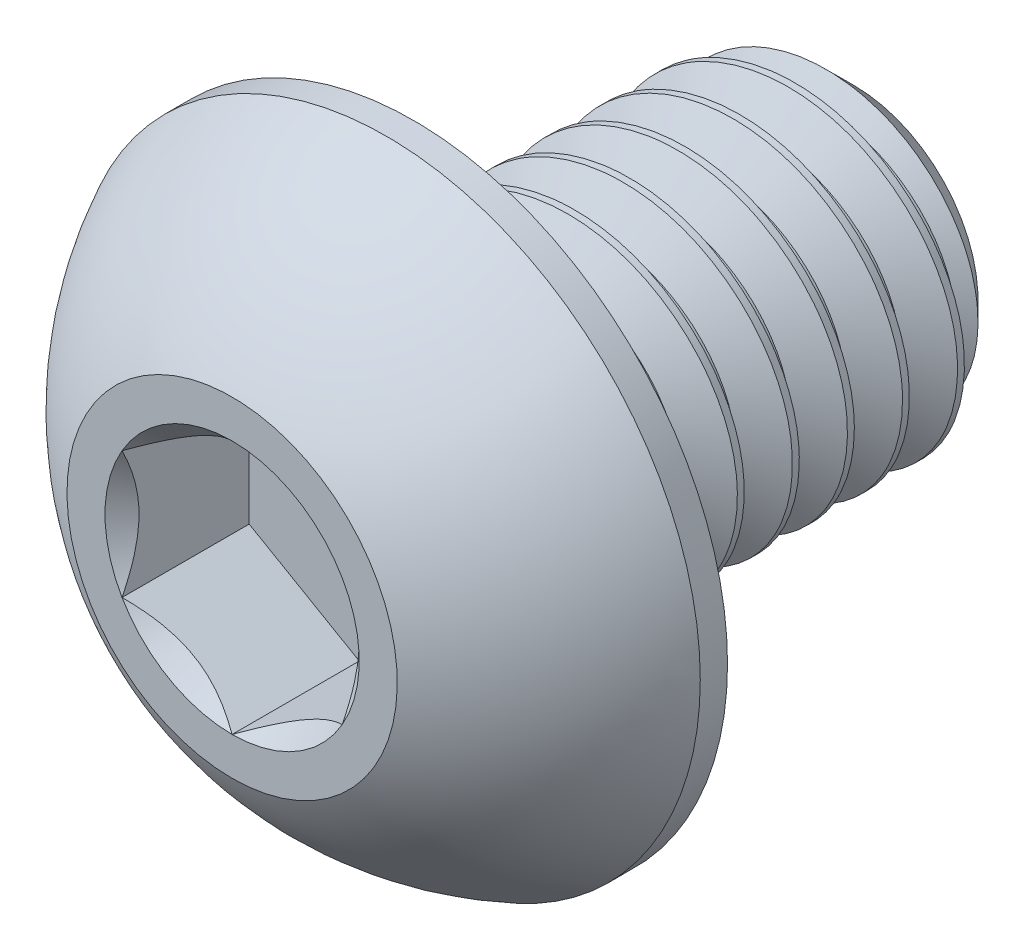
SolidWorks part; units mm, degrees
ref_plane "Front" through (0, 0, 0) normal (0, 0, 1) x (1, 0, 0)
ref_plane "Top" through (0, 0, 0) normal (0, 1, 0) x (1, 0, 0)
ref_plane "Right" through (0, 0, 0) normal (1, 0, 0) x (0, 0, -1)
sketch "Sketch1" plane through (0, 0, 0) normal (1, 0, 0) x (0, 0, -1)
  line L2 (1.65, 1.5) -> (5.65, 1.5)
  line L3 (5.65, 1.5) -> (5.65, 0)
  line L4 (5.65, 0) -> (1.65, 0)
  line L6 (1.4025, 2.85) -> (1.65, 2.85) construction
  line L7 (5.65, 1.5) -> (5.65, -1.5) construction
  line L8 (0, 0) -> (1.65, 0) construction
  line L9 (1.65, 2.85) -> (1.65, -2.85) construction
  line L11 (1.65, 1.5) -> (1.65, 0)
  line L13 (0, 1) -> (0, -1) construction
  line L14 (0, 1) -> (0, 1.5) construction
  arc A3 (0, 1.5) -> (1.4025, 2.85) centre (2.7948, 0) cw construction
  dimension "D1" = 0.2475
revolve "Revolve1" add sketch "Sketch1" angle 360 mid plane about L4
sketch "Sketch3" plane through (0, 0, -5.65) normal (0, 0, -1) x (-1, 0, 0)
  circle A0 centre (0, 0) radius 1.5
curve "Helix/Spiral1" pitch 0.5 height 4.5 radius 1.5 centre (0, 0, -5.65) axis (0, 0, 1) start towards (1, 0, 0)
sketch "Sketch2" plane through (0, 0, 0) normal (1, 0, 0) x (0, 0, -1)
  line L0 (5.525, 1.5) -> (5.9625, 1.5) construction
  line L1 (5.9625, 1.5) -> (5.7437, 1.1211) construction
  line L2 (5.7437, 1.1211) -> (5.525, 1.5) construction
  line L3 (5.6187, 1.3376) -> (5.8687, 1.3376) construction
  line L4 (5.7125, 1.1752) -> (5.775, 1.1752) construction
  line L5 (5.7437, 1.1752) -> (5.7437, 1.5) construction
  line L6 (5.525, 1.5) -> (5.9625, 1.5)
  line L7 (5.9625, 1.5) -> (5.775, 1.1752)
  line L8 (5.775, 1.1752) -> (5.7125, 1.1752)
  line L9 (5.7125, 1.1752) -> (5.525, 1.5)
  point P9 (5.7437, 1.3376)
  dimension "D1" = 0.25
  dimension "D2" = 0.0625
chamfer "Chamfer1" distance 0.375 angle 45 1 edges at (0, 1.5, -5.65)
sweep "Cut-Sweep1" cut profiles "Sketch2" path "Helix/Spiral1" align with end faces yes
sketch "Sketch7" plane through (0, 0, 0) normal (1, 0, 0) x (0, 0, -1)
  line L6 (1.4025, 2.85) -> (1.65, 2.85) construction
  line L8 (0, 0) -> (1.65, 0) construction
  line L11 (1.65, 2.85) -> (1.65, -2.85) construction
  line L12 (1.4025, 2.85) -> (1.65, 2.85)
  line L13 (0, 0) -> (1.65, 0)
  line L14 (0, 1) -> (0, -1) construction
  line L15 (1.65, 2.85) -> (1.65, 0)
  line L16 (0, 1.5) -> (0, 0)
  arc A2 (1.4025, 2.85) -> (0, 1.5) centre (2.7948, 0) ccw construction
  arc A3 (1.4025, 2.85) -> (0, 1.5) centre (2.7948, 0) ccw
revolve "Revolve2" add sketch "Sketch7" angle 360 mid plane about L13
sketch "Sketch5" plane through (0, 0, 0) normal (0, 0, 1) x (1, 0, 0)
  line L1 (1, -0.5774) -> (1, 0.5774)
  line L2 (1, 0.5774) -> (0, 1.1547)
  line L3 (0, 1.1547) -> (-1, 0.5774)
  line L4 (-1, 0.5774) -> (-1, -0.5774)
  line L5 (-1, -0.5774) -> (0, -1.1547)
  line L6 (0, -1.1547) -> (1, -0.5774)
  circle A0 centre (0, 0) radius 1 construction
extrude "Cut-Extrude2" cut sketch "Sketch5" against normal blind 1.155
sketch "Sketch6" plane through (0, 0, 0) normal (0, 0, 1) x (1, 0, 0)
  circle A0 centre (0, 0) radius 1.1547
extrude "Cut-Extrude3" cut sketch "Sketch6" against normal blind 1.155 draft 45
sketch "Sketch9" [suppressed] plane through (0, 0, -5.0546) normal (0, 0, 1) x (1, 0, 0)
  circle A2 centre (0, 0) radius 4.7625
extrude "Boss-Extrude2" [suppressed] add sketch "Sketch9" against normal offset from surface (6.35 mm away) 31.75 up to face at (0, 1.125, -5.65)
sketch "Sketch10" plane through (0, 0, 0) normal (1, 0, 0) x (0, 0, -1)
  line L0 (5.65, 1.5) -> (5.65, -1.5) construction
  point P0 (4.9, -1.5)
  dimension "D1" = 0.75
equation "\"D3@Helix/Spiral1\"=\"Lg@Sketch1\" + (\"D4@Helix/Spiral1\")"
equation "\"D1@Chamfer1\" = \"D4@Helix/Spiral1\" * .75"
equation "\"D1@Cut-Extrude2\" = \"Head Ht@Sketch1\" * .7"
equation "\"D1@Sketch1\" = \"Head Ht@Sketch1\" * .15"
equation "\"D1@Sketch10\" = \"D4@Helix/Spiral1\" * 1.5"
equation "\"D1@Cut-Extrude3\" = \"D1@Cut-Extrude2\""
equation "\"D1@Sketch2\"=\"D4@Helix/Spiral1\"*.5"
equation "\"D2@Sketch2\"=\"D4@Helix/Spiral1\"*.125"
